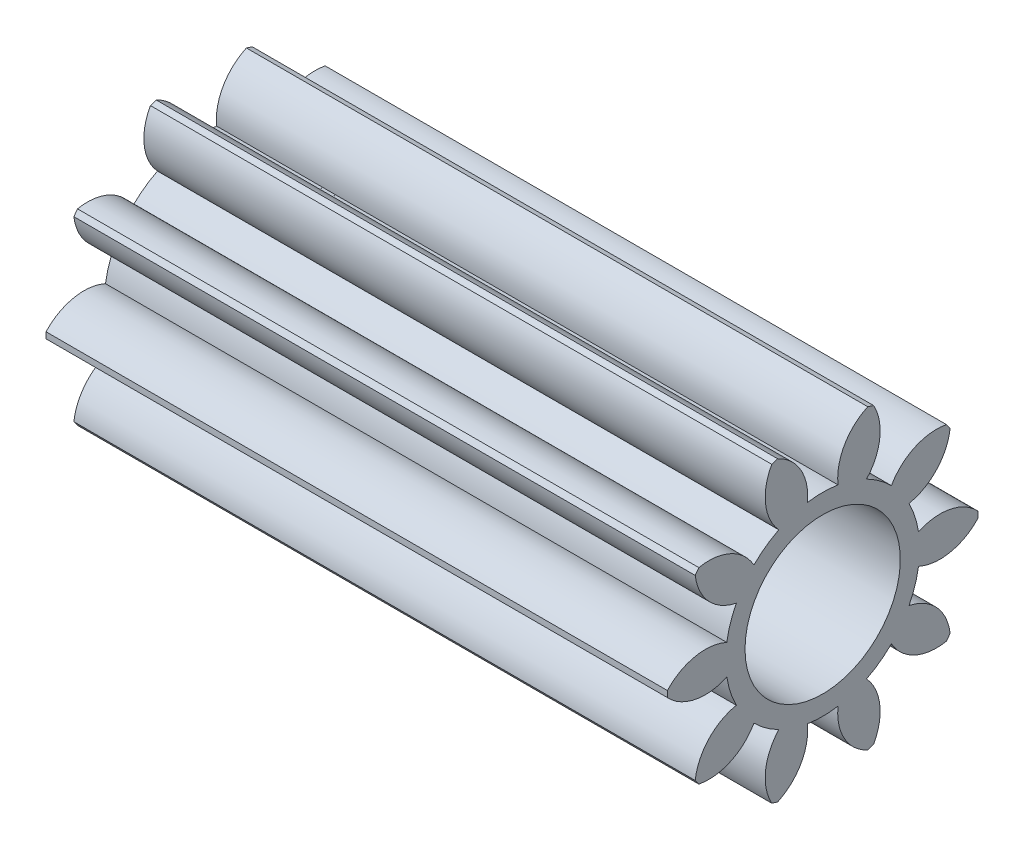
SolidWorks part; units mm, degrees
ref_plane "Plane1" through (0, 0, 0) normal (0, 0, 1) x (1, 0, 0)
ref_plane "Plane2" through (0, 0, 0) normal (0, 1, 0) x (1, 0, 0)
ref_plane "Plane3" through (0, 0, 0) normal (1, 0, 0) x (0, 0, -1)
sketch "HoldingSke" plane through (0, 0, 0) normal (0, 1, 0) x (1, 0, 0)
  line L0 (0, 0) -> (1.9696, -0.3473)
  line L1 (-15, 0) -> (100, 0) construction
  line L2 (0, 0) -> (-2.1039, 2.3779)
  line L3 (0, 0) -> (-11.863, 4.5341)
  line L4 (0, 0) -> (8.5048, 1.4996)
  line L5 (0, 0) -> (-46.8476, -17.4728)
  line L6 (0, 0) -> (-9.9476, -6.7116)
  line L7 (-2.1039, 2.3779) -> (8.6586, 51.2059)
  line L8 (-76.2, 54.61) -> (-75.7, 54.61)
  line L9 (-71.009, 38.7566) -> (-53.1078, 45.2721)
  line L10 (-76.2, 71.12) -> (104.1128, 71.12)
  line L11 (0, 0) -> (-12, 0)
  line L12 (-76.2, 101.6) -> (-76.181, 101.6)
  line L13 (24.9733, 27.94) -> (52.9518, 28.4284)
  line L14 (24.9733, 27.94) -> (24.9743, 27.94)
  line L15 (24.9733, 27.94) -> (100.4006, 29.5858)
  line L16 (-63.627, -0.5) -> (-12.827, -0.5)
  circle A0 centre (0, 0) radius 1.5
  circle A1 centre (0, 0) radius 1.874
  circle A2 centre (0, 0) radius 37.5
  circle A3 centre (0, 0) radius 1.5
  dimension "Num_teeth" = 10
  dimension "Pitch_radius" = 180.3128
  dimension "Width" = 12
  dimension "Thickness" = 12
sketch "BasProSke" plane through (0, 0, 0) normal (0, 1, 0) x (1, 0, 0)
  line L0 (-10, 0) -> (60, 0) construction
  line L1 (0, 0) -> (0, 3)
  line L2 (0, 0) -> (12, 0)
  line L3 (12, 0) -> (12, 3)
  line L4 (12, 3) -> (0, 3)
  dimension "Thickness" = 12
  dimension "Diameter" = 6
revolve "Base-Revolve" add sketch "BasProSke" angle 360 about L0
sketch "TooCutSke" plane through (0, 0, 0) normal (1, 0, 0) x (0, 0, -1)
  line L1 (0, 0) -> (0, 107) construction
  line L2 (0, 0) -> (-0.4243, 2.4637) construction
  line L3 (0, 0) -> (-1.5292, 4.7063) construction
  line L4 (-0.4243, 2.4637) -> (-0.7646, 2.3532) construction
  arc A0 (0.2964, 1.8504) -> (-0.2964, 1.8504) centre (0, 0) ccw
  arc A1 (0.9059, 2.8866) -> (-0.9059, 2.8866) centre (0, 0) ccw
  circle A2 centre (0, 0) radius 2.5 construction
  circle A3 centre (0, 0) radius 2.3492 construction
  arc A4 (-0.2964, 1.8504) -> (-0.9059, 2.8866) centre (-1.2901, 1.9633) ccw
  arc A5 (0.9059, 2.8866) -> (0.2964, 1.8504) centre (1.2901, 1.9633) ccw
extrude "ToothCut" cut sketch "TooCutSke" along normal through all
fillet "Breaks" [suppressed] radius 0.01 tangent propagation no
fillet "RootFillets" [suppressed] radius 0.126
pattern_circular "TeethCuts" count 10 every 36 about axis through (-10, 0, 0) along (1, 0, 0) of "ToothCut", "RootFillets", "Breaks"
sketch "HubNeaOneSke" plane through (0, 0, 0) normal (-1, 0, 0) x (0, 0, 1)
  circle A0 centre (0, 0) radius 1.874
  dimension "Diameter" = 3.748
extrude "HubNearOne" [suppressed] add sketch "HubNeaOneSke" along normal blind 38.0001
sketch "HubNeaBotSke" plane through (0, 0, 0) normal (-1, 0, 0) x (0, 0, 1)
  circle A0 centre (0, 0) radius 1.874
  dimension "Diameter" = 3.748
extrude "HubNearBoth" [suppressed] add sketch "HubNeaBotSke" along normal blind 19
ref_plane "FarPln" through (12, 0, 0) normal (1, 0, 0) x (0, 0, -1)
sketch "HubFarSke" plane through (12, 0, 0) normal (1, 0, 0) x (0, 0, -1)
  circle A0 centre (0, 0) radius 1.874
  dimension "Diameter" = 3.748
extrude "HubFar" [suppressed] add sketch "HubFarSke" along normal blind 19
sketch "BorSke" plane through (0, 0, 0) normal (1, 0, 0) x (0, 0, -1)
  circle A0 centre (0, 0) radius 1.5
  dimension "Diameter" = 3
extrude "Bore" cut sketch "BorSke" along normal mid plane 100.0001
sketch "KeySke" plane through (0, 0, 0) normal (1, 0, 0) x (0, 0, -1)
  line L0 (-0.6, 0) -> (-0.6, 2)
  line L1 (-0.6, 2) -> (0.6, 2)
  line L2 (0.6, 2) -> (0.6, 0)
  line L3 (0, 0) -> (0, 34) construction
  line L4 (-0.6, 0) -> (0.6, 0)
extrude "Keyway" [suppressed] cut sketch "KeySke" along normal mid plane 100.0001
pattern_circular "Keyway2" [suppressed] count 2 every 90 about axis through (-10, 0, 0) along (1, 0, 0) reverse direction yes
equation "' \"Module@HoldingSke\" = 6.35"
equation "' \"Num_teeth@HoldingSke\" = 12"
equation "' \"Ap@HoldingSke\" =  20"
equation "' \"Ap@HoldingSke\" = 20"
equation "' \"Width@HoldingSke\" = 0.5 * 25.4"
equation "' \"Hub_dia@HoldingSke\"= 1 * 25.4"
equation "' \"Hub_dia@HoldingSke\" = 1 * 25.4"
equation "' \"Overall_len@HoldingSke\" = 1.0 * 25.4"
equation "' \"Bore@HoldingSke\" = 0.75 * 25.4"
equation "' \"T_dim@HoldingSke\" = 0.1 * 25.4"
equation "' \"Width@KeySke\" = 0.25 * 25.4"
equation "' \"Show_teeth@HoldingSke\" = 13"
equation "' \"Backlash@HoldingSke\" = 0.009 * 25.4"
equation "' \"Addendum_fac@HoldingSke\" = 1.0"
equation "' \"Dedendum_fac@HoldingSke\" = 1.25"
equation "' \"Dedendum_add@HoldingSke\" = 0.00005 * 25.4"
equation "' \"Clearance_fac@HoldingSke\" = 0.25"
equation "\"Pitch@HoldingSke\" = 1 / \"Module@HoldingSke\""
equation "\"Overcut_dia@TooCutSke\" = (\"Num_teeth@HoldingSke\" + 2 * \"Addendum_fac@HoldingSke\") / \"Pitch@HoldingSke\" + 0.002 * 25.4"
equation "\"Pitch_dia@TooCutSke\" = \"Num_teeth@HoldingSke\" / \"Pitch@HoldingSke\""
equation "\"Base_dia@TooCutSke\" = \"Num_teeth@HoldingSke\" / \"Pitch@HoldingSke\" * cos((\"Ap@HoldingSke\"  * 3.14159265 / 180))"
equation "\"Root_dia@TooCutSke\" = (\"Num_teeth@HoldingSke\" + 2) / \"Pitch@HoldingSke\" - 2 * (\"Addendum_fac@HoldingSke\" + \"Dedendum_fac@HoldingSke\") / \"Pitch@HoldingSke\" - \"Dedendum_add@HoldingSke\" * 2"
equation "\"Half_ang@TooCutSke\" = 180 / \"Num_teeth@HoldingSke\""
equation "\"Half_CT@TooCutSke\" = \"Num_teeth@HoldingSke\" / \"Pitch@HoldingSke\" * sin((3.14159265 / 2 / \"Num_teeth@HoldingSke\")) / 2 - 7 * \"Backlash@HoldingSke\" / 4"
equation "\"Flank_rad@TooCutSke\" = \"Num_teeth@HoldingSke\" / \"Pitch@HoldingSke\" / 5"
equation "\"Radius@RootFillets\" = \"Clearance_fac@HoldingSke\" / \"Pitch@HoldingSke\" + \"Dedendum_add@HoldingSke\""
equation "\"Break_rad@Breaks\" = 0.02 / \"Pitch@HoldingSke\""
equation "\"Thickness@HoldingSke\" = \"Width@HoldingSke\""
equation "\"OAL@HoldingSke\" = \"Thickness@HoldingSke\""
equation "\"MHD@HoldingSke\" = (\"Num_teeth@HoldingSke\" + 2) / \"Pitch@HoldingSke\" - 2 * (\"Addendum_fac@HoldingSke\" + \"Dedendum_fac@HoldingSke\")  / \"Pitch@HoldingSke\" - \"Dedendum_add@HoldingSke\" * 2"
equation "\"MBD@HoldingSke\" = (\"Num_teeth@HoldingSke\" + 2) / \"Pitch@HoldingSke\" - 2 * (\"Addendum_fac@HoldingSke\" + \"Dedendum_fac@HoldingSke\")  / \"Pitch@HoldingSke\" - \"Dedendum_add@HoldingSke\" * 2 - 0.002 * 25.4"
equation "\"MHD@HoldingSke\" = ((sgn( \"MHD@HoldingSke\" - \"Hub_dia@HoldingSke\" )-1)*( \"MHD@HoldingSke\" - \"Hub_dia@HoldingSke\" ))/-2+ \"Hub_dia@HoldingSke\""
equation "\"MBD@HoldingSke\" = ((sgn( \"MBD@HoldingSke\" - \"Bore@HoldingSke\" )-1)*( \"MBD@HoldingSke\" - \"Bore@HoldingSke\" ))/-2+ \"Bore@HoldingSke\""
equation "\"OAL@HoldingSke\" = ((sgn( \"OAL@HoldingSke\" - \"Overall_len@HoldingSke\" )+1)*( \"OAL@HoldingSke\" - \"Overall_len@HoldingSke\" ))/2 + \"Overall_len@HoldingSke\" + 0.000002 * 25.4"
equation "\"Num_teeth@TeethCuts\" = int( \"Show_teeth@HoldingSke\" ) + 1"
equation "\"Num_teeth@TeethCuts\" = ((sgn( \"Num_teeth@TeethCuts\" - \"Num_teeth@HoldingSke\" )-1)*( \"Num_teeth@TeethCuts\" - \"Num_teeth@HoldingSke\" ))/-2+ \"Num_teeth@HoldingSke\""
equation "\"Num_teeth@TeethCuts\" = ((sgn( \"Num_teeth@TeethCuts\" - 2.0)+1)*( \"Num_teeth@TeethCuts\" - 2.0))/2 +2.0"
equation "\"Angle@TeethCuts\" = 360.0 / \"Num_teeth@HoldingSke\""
equation "\"Diameter@BasProSke\" = (\"Num_teeth@HoldingSke\" + 2 * \"Addendum_fac@HoldingSke\") / \"Pitch@HoldingSke\""
equation "\"Thickness@BasProSke\"  = \"Thickness@HoldingSke\""
equation "' \"Fillet_rad@BasProSke\" =  \"Thickness@HoldingSke\" * 0.05"
equation "' \"Fillet_rad@BasProSke\" = \"Thickness@HoldingSke\" * 0.05"
equation "\"MHD@HoldingSke\" = ((sgn( \"MHD@HoldingSke\" - \"Root_dia@TooCutSke\" )-1)*( \"MHD@HoldingSke\" - \"Root_dia@TooCutSke\" ))/-2+ \"Root_dia@TooCutSke\""
equation "\"Diameter@HubNeaOneSke\" = \"MHD@HoldingSke\""
equation "\"Length@HubNearOne\" = \"OAL@HoldingSke\" - \"Thickness@BasProSke\""
equation "\"Diameter@HubNeaBotSke\" = \"MHD@HoldingSke\""
equation "\"Length@HubNearBoth\" = ( \"OAL@HoldingSke\" - \"Thickness@BasProSke\" ) / 2.0"
equation "\"Thickness@FarPln\" = \"Thickness@BasProSke\""
equation "\"Diameter@HubFarSke\" = \"MHD@HoldingSke\""
equation "\"Length@HubFar\" = ( \"OAL@HoldingSke\" - \"Thickness@BasProSke\" ) / 2.0"
equation "\"Diameter@BorSke\" = \"MBD@HoldingSke\""
equation "\"D1@Bore\" = \"OAL@HoldingSke\" * 2.0"
equation "\"D1@Keyway\" = \"OAL@HoldingSke\" * 2.0"
equation "\"Offset@KeySke\" = \"T_dim@HoldingSke\" + \"MBD@HoldingSke\" / 2.0"
